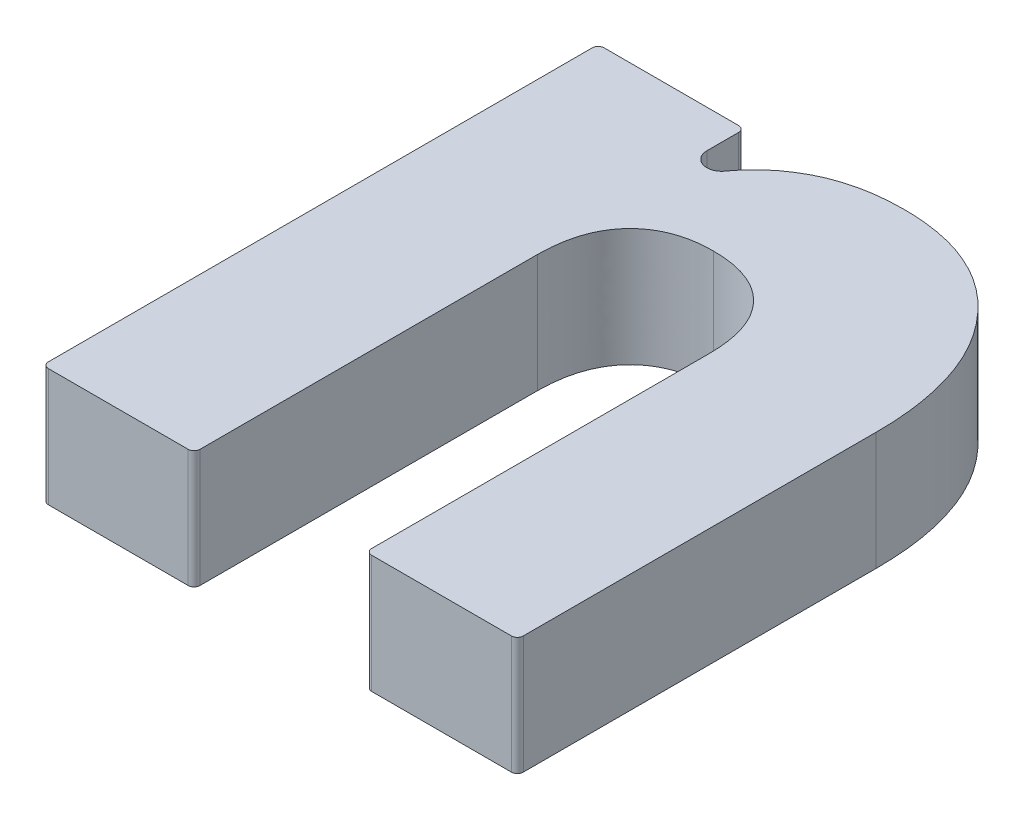
SolidWorks part; units mm, degrees
ref_plane "Front Plane" through (0, 0, 0) normal (0, 0, 1) x (1, 0, 0)
ref_plane "Top Plane" through (0, 0, 0) normal (0, 1, 0) x (1, 0, 0)
ref_plane "Right Plane" through (0, 0, 0) normal (1, 0, 0) x (0, 0, -1)
sketch "Sketch1" plane through (0, 0, 0) normal (0, 1, 0) x (1, 0, 0)
  line L0 (11.2961, 0) -> (11.2961, 94.1835)
  line L1 (11.2961, 94.1835) -> (36.1177, 94.1835)
  line L2 (36.1177, 94.1835) -> (36.1187, 76.199)
  line L5 (91.7806, 60.7907) -> (91.7806, 0)
  line L6 (91.7806, 0) -> (66.092, 0)
  line L7 (66.092, 0) -> (66.092, 58.2144)
  line L8 (36.9847, 58.2144) -> (36.9847, 0)
  line L9 (36.9847, 0) -> (11.2961, 0)
  line L10 (36.1187, 76.199) -> (36.1187, 73.6982)
  spline S0 degree 3 poles (36.1187, 73.6982) (36.454, 75.2873) (36.8125, 77.7413) (37.779, 80.9008) (38.7453, 83.1822) (39.9184, 85.3114) (41.3061, 87.2806) (42.9297, 89.0558) (44.7039, 90.682) (46.677, 92.0566) (48.7647, 93.2639) (51.0166, 94.2381) (53.4229, 94.9645) (56.8935, 95.7246) (59.6132, 95.8937) (61.4596, 95.8928) knots 0 0 0 0 0.130484 0.19842 0.264656 0.329039 0.393226 0.457524 0.521821 0.586009 0.650138 0.715156 0.782458 0.851624 1 1 1 1
  spline S1 degree 3 poles (61.4596, 95.8928) (63.6427, 95.895) (66.8604, 95.6226) (70.9756, 94.619) (73.8192, 93.5467) (76.5132, 92.2017) (79.009, 90.5271) (81.3687, 88.5864) (83.506, 86.3222) (85.4567, 83.8402) (87.1574, 81.1335) (88.5979, 78.2304) (89.7557, 75.1127) (90.6767, 71.8161) (91.5452, 67.0384) (91.7961, 63.326) (91.7806, 60.7907) knots 0 0 0 0 0.125406 0.184536 0.242771 0.29962 0.357108 0.415044 0.474759 0.535579 0.596114 0.658053 0.721395 0.786875 0.854415 1 1 1 1
  spline S2 degree 3 poles (66.092, 58.2144) (66.0786, 60.4072) (65.7235, 63.6249) (64.0311, 67.3966) (62.3076, 69.6463) (60.1617, 71.4546) (56.5673, 73.2114) (53.483, 73.648) (51.3773, 73.6227) knots 0 0 0 0 0.273114 0.393618 0.508303 0.621707 0.738476 1 1 1 1
  spline S3 degree 3 poles (51.3773, 73.6227) (49.3176, 73.6372) (46.2816, 73.2248) (42.7828, 71.4375) (40.6657, 69.654) (38.9995, 67.3848) (37.331, 63.6225) (37.0174, 60.401) (36.9847, 58.2144) knots 0 0 0 0 0.259191 0.374425 0.488234 0.602886 0.724235 1 1 1 1
  point P1 (0, 0)
  point P2 (36.1187, 73.6982)
  point P3 (0, 0)
extrude "Boss-Extrude4" add sketch "Sketch1" against normal blind 20
fillet "Fillet1" radius 2.5 1 edges at (36.1187, -10, -73.6982)
fillet "Fillet2" radius 1 6 edges at (91.7806, -10, 0) (66.092, -10, 0) (36.9847, -10, 0) (11.2961, -10, 0) (11.2961, -10, -94.1835) (36.1177, -10, -94.1835)
